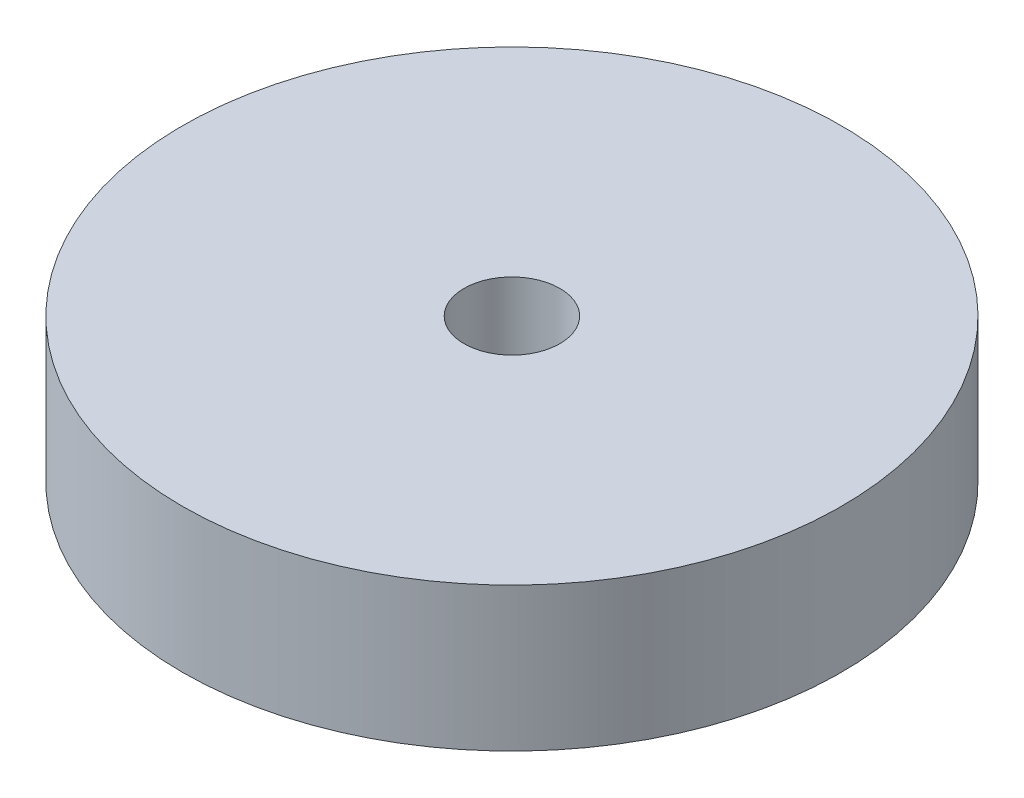
SolidWorks part; units mm, degrees
ref_plane "Front Plane" through (0, 0, 0) normal (0, 0, 1) x (1, 0, 0)
ref_plane "Top Plane" through (0, 0, 0) normal (0, 1, 0) x (1, 0, 0)
ref_plane "Right Plane" through (0, 0, 0) normal (1, 0, 0) x (0, 0, -1)
sketch "Sketch1" plane through (0, 0, 0) normal (0, 1, 0) x (1, 0, 0)
  circle A0 centre (0, 0) radius 24.384 construction
  circle A1 centre (0, 0) radius 34.384
  dimension "D1" = 48.768
  dimension "D2" = 10
extrude "Boss-Extrude1" add sketch "Sketch1" along normal blind 15
hole_wizard "Ø10.0mm Dowel Hole1" positions "Sketch3" profile "Sketch2" hole size "Ø10.0" standard "ANSI Metric" end condition through all
sketch "Sketch3" plane through (0, 0, 0) normal (0, -1, 0) x (-1, 0, 0)
  point P0 (0, 0)
sketch "Sketch2" plane through (0, 0, 0) normal (1, 0, 0) x (0, 0, -1)
  line L0 (0, 0) -> (0, 15)
  line L1 (0, 15) -> (5, 15)
  line L2 (5, 15) -> (5, 0)
  line L5 (5, 0) -> (0, 0)
  line L11 (0, -6.35) -> (0, 107.95) construction
  dimension "Thru Hole Dia." = 10
  dimension "Thru Hole Depth" = 15
sketch "Sketch4" plane through (0, 0, 0) normal (0, -1, 0) x (-1, 0, 0)
  line L1 (-3.8971, -6.75) -> (3.8971, -6.75)
  line L2 (3.8971, -6.75) -> (7.7942, 0)
  line L3 (7.7942, 0) -> (3.8971, 6.75)
  line L4 (3.8971, 6.75) -> (-3.8971, 6.75)
  line L5 (-3.8971, 6.75) -> (-7.7942, 0)
  line L6 (-7.7942, 0) -> (-3.8971, -6.75)
  circle A0 centre (0, 0) radius 6.75 construction
  dimension "D1" = 13.5
extrude "Cut-Extrude1" cut sketch "Sketch4" against normal blind 7.5
